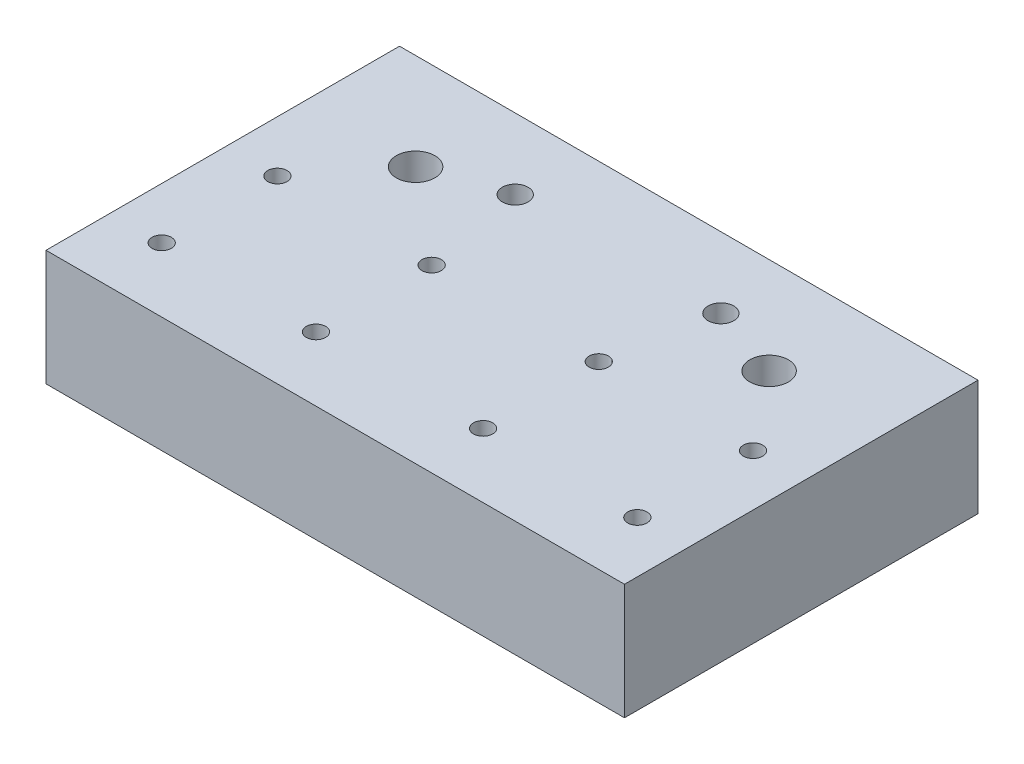
SolidWorks part; units mm, degrees
ref_plane "Front Plane" through (0, 0, 0) normal (0, 0, 1) x (1, 0, 0)
ref_plane "Top Plane" through (0, 0, 0) normal (0, 1, 0) x (1, 0, 0)
ref_plane "Right Plane" through (0, 0, 0) normal (1, 0, 0) x (0, 0, -1)
sketch "Sketch1" plane through (0, 0, 0) normal (0, 1, 0) x (1, 0, 0)
  line L0 (0, -383.892) -> (0, 18810.7071) construction
  line L1 (-45, 30) -> (45, 30)
  line L2 (-45, 30) -> (-45, -25)
  line L3 (-45, -25) -> (45, -25)
  line L4 (45, 30) -> (45, -25)
  line L7 (-383.892, 0) -> (18810.7071, 0) construction
  line L14 (25, -383.892) -> (25, 18810.7071) construction
  line L16 (13, -15) -> (37, -15) construction
  line L18 (13, -15) -> (13, 3) construction
  line L19 (13, 3) -> (37, 3) construction
  line L20 (37, -15) -> (37, 3) construction
  line L21 (13, -15) -> (37, 3) construction
  line L22 (13, 3) -> (37, -15) construction
  circle A0 centre (27.5, 15) radius 3
  circle A1 centre (-27.5, 15) radius 3
  circle A2 centre (37, 3) radius 1.5
  circle A3 centre (13, 3) radius 1.5
  circle A4 centre (37, -15) radius 1.5
  circle A5 centre (13, -15) radius 1.5
  circle A6 centre (-37, -15) radius 1.5
  circle A7 centre (-37, 3) radius 1.5
  circle A8 centre (-13, -15) radius 1.5
  circle A9 centre (-13, 3) radius 1.5
  point P0 (0, 0)
  point P19 (25, -6)
  dimension "D6" = 6
  dimension "D7" = 27.5
  dimension "D8" = 40
  dimension "D13" = 3
  dimension "D15" = 18
  dimension "D2" = 90
  dimension "D3" = 30
  dimension "D4" = 25
  dimension "D5" = 45
  dimension "D10" = 24
  dimension "D11" = 18
  dimension "D12" = 10
  dimension "D9" = 25
  dimension "D14" = 2
extrude "Boss-Extrude1" add sketch "Sketch1" along normal blind 18
sketch "Sketch2" plane through (0, 18, 0) normal (0, 1, 0) x (1, 0, 0)
  line L0 (45, -25) -> (45, 30) construction
  line L3 (0, -1000) -> (0, 49000) construction
  line L4 (45, 30) -> (-45, 30) construction
  circle A0 centre (16, 19) radius 2
  circle A3 centre (-16, 19) radius 2
  dimension "D1" = 11
  dimension "D2" = 4
  dimension "D3" = 29
extrude "Cut-Extrude1" cut sketch "Sketch2" against normal up to next
